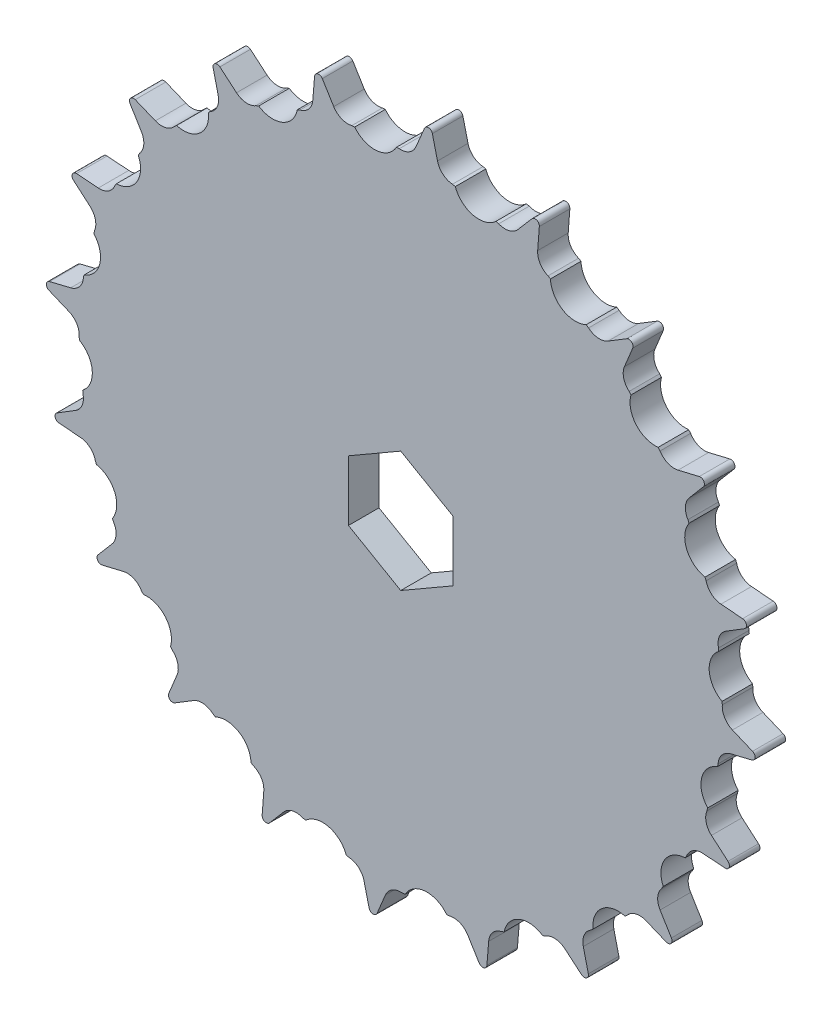
SolidWorks part; units mm, degrees
ref_plane "Front Plane" through (0, 0, 0) normal (0, 0, 1) x (1, 0, 0)
ref_plane "Top Plane" through (0, 0, 0) normal (0, 1, 0) x (1, 0, 0)
ref_plane "Right Plane" through (0, 0, 0) normal (1, 0, 0) x (0, 0, -1)
sketch "Sketch1" plane through (0, 0, 0) normal (0, 0, 1) x (1, 0, 0)
  line L0 (3.6626, 79.3215) -> (5.6677, 84.1262)
  line L1 (3.6626, 79.3215) -> (8.7911, 78.9179) construction
  line L2 (7.5623, 83.9771) -> (8.7911, 78.9179)
  line L3 (3.6626, 79.3215) -> (0, 0) construction
  line L4 (0, 0) -> (8.7911, 78.9179) construction
  line L5 (16.0261, 77.772) -> (18.7582, 82.2038)
  line L6 (20.6061, 81.7602) -> (21.0283, 76.5711)
  line L7 (27.995, 74.3074) -> (31.3867, 78.2573)
  line L8 (33.1425, 77.5301) -> (32.7478, 72.3388)
  line L9 (39.2746, 69.0132) -> (43.2424, 72.3839)
  line L10 (44.8629, 71.3909) -> (43.6609, 66.3253)
  line L11 (49.5871, 62.0196) -> (54.0334, 64.7281)
  line L12 (55.4785, 63.4939) -> (53.4989, 58.6786)
  line L13 (58.6786, 53.4989) -> (63.4939, 55.4785)
  line L14 (64.7281, 54.0334) -> (62.0196, 49.5871)
  line L15 (66.3253, 43.6609) -> (71.3909, 44.8629)
  line L16 (72.3839, 43.2424) -> (69.0132, 39.2746)
  line L17 (72.3388, 32.7478) -> (77.5301, 33.1425)
  line L18 (78.2573, 31.3867) -> (74.3074, 27.995)
  line L19 (76.5711, 21.0283) -> (81.7602, 20.6061)
  line L20 (82.2038, 18.7582) -> (77.772, 16.0261)
  line L21 (78.9179, 8.7911) -> (83.9771, 7.5623)
  line L22 (84.1262, 5.6677) -> (79.3215, 3.6626)
  line L23 (79.3215, -3.6626) -> (84.1262, -5.6677)
  line L24 (83.9771, -7.5623) -> (78.9179, -8.7911)
  line L25 (77.772, -16.0261) -> (82.2038, -18.7582)
  line L26 (81.7602, -20.6061) -> (76.5711, -21.0283)
  line L27 (74.3074, -27.995) -> (78.2573, -31.3867)
  line L28 (77.5301, -33.1425) -> (72.3388, -32.7478)
  line L29 (69.0132, -39.2746) -> (72.3839, -43.2424)
  line L30 (71.3909, -44.8629) -> (66.3253, -43.6609)
  line L31 (62.0196, -49.5871) -> (64.7281, -54.0334)
  line L32 (63.4939, -55.4785) -> (58.6786, -53.4989)
  line L33 (53.4989, -58.6786) -> (55.4785, -63.4939)
  line L34 (54.0334, -64.7281) -> (49.5871, -62.0196)
  line L35 (43.6609, -66.3253) -> (44.8629, -71.3909)
  line L36 (43.2424, -72.3839) -> (39.2746, -69.0132)
  line L37 (32.7478, -72.3388) -> (33.1425, -77.5301)
  line L38 (31.3867, -78.2573) -> (27.995, -74.3074)
  line L39 (21.0283, -76.5711) -> (20.6061, -81.7602)
  line L40 (18.7582, -82.2038) -> (16.0261, -77.772)
  line L41 (8.7911, -78.9179) -> (7.5623, -83.9771)
  line L42 (5.6677, -84.1262) -> (3.6626, -79.3215)
  line L43 (-3.6626, -79.3215) -> (-5.6677, -84.1262)
  line L44 (-7.5623, -83.9771) -> (-8.7911, -78.9179)
  line L45 (-16.0261, -77.772) -> (-18.7582, -82.2038)
  line L46 (-20.6061, -81.7602) -> (-21.0283, -76.5711)
  line L47 (-27.995, -74.3074) -> (-31.3867, -78.2573)
  line L48 (-33.1425, -77.5301) -> (-32.7478, -72.3388)
  line L49 (-39.2746, -69.0132) -> (-43.2424, -72.3839)
  line L50 (-44.8629, -71.3909) -> (-43.6609, -66.3253)
  line L51 (-49.5871, -62.0196) -> (-54.0334, -64.7281)
  line L52 (-55.4785, -63.4939) -> (-53.4989, -58.6786)
  line L53 (-58.6786, -53.4989) -> (-63.4939, -55.4785)
  line L54 (-64.7281, -54.0334) -> (-62.0196, -49.5871)
  line L55 (-66.3253, -43.6609) -> (-71.3909, -44.8629)
  line L56 (-72.3839, -43.2424) -> (-69.0132, -39.2746)
  line L57 (-72.3388, -32.7478) -> (-77.5301, -33.1425)
  line L58 (-78.2573, -31.3867) -> (-74.3074, -27.995)
  line L59 (-76.5711, -21.0283) -> (-81.7602, -20.6061)
  line L60 (-82.2038, -18.7582) -> (-77.772, -16.0261)
  line L61 (-78.9179, -8.7911) -> (-83.9771, -7.5623)
  line L62 (-84.1262, -5.6677) -> (-79.3215, -3.6626)
  line L63 (-79.3215, 3.6626) -> (-84.1262, 5.6677)
  line L64 (-83.9771, 7.5623) -> (-78.9179, 8.7911)
  line L65 (-77.772, 16.0261) -> (-82.2038, 18.7582)
  line L66 (-81.7602, 20.6061) -> (-76.5711, 21.0283)
  line L67 (-74.3074, 27.995) -> (-78.2573, 31.3867)
  line L68 (-77.5301, 33.1425) -> (-72.3388, 32.7478)
  line L69 (-69.0132, 39.2746) -> (-72.3839, 43.2424)
  line L70 (-71.3909, 44.8629) -> (-66.3253, 43.6609)
  line L71 (-62.0196, 49.5871) -> (-64.7281, 54.0334)
  line L72 (-63.4939, 55.4785) -> (-58.6786, 53.4989)
  line L73 (-53.4989, 58.6786) -> (-55.4785, 63.4939)
  line L74 (-54.0334, 64.7281) -> (-49.5871, 62.0196)
  line L75 (-43.6609, 66.3253) -> (-44.8629, 71.3909)
  line L76 (-43.2424, 72.3839) -> (-39.2746, 69.0132)
  line L77 (-32.7478, 72.3388) -> (-33.1425, 77.5301)
  line L78 (-31.3867, 78.2573) -> (-27.995, 74.3074)
  line L79 (-21.0283, 76.5711) -> (-20.6061, 81.7602)
  line L80 (-18.7582, 82.2038) -> (-16.0261, 77.772)
  line L81 (-8.7911, 78.9179) -> (-7.5623, 83.9771)
  line L82 (-5.6677, 84.1262) -> (-3.6626, 79.3215)
  line L83 (0, 80.85) -> (0, 0) construction
  line L84 (0, 0) -> (6.5906, 83.7411) construction
  circle A0 centre (0, 0) radius 80.85 construction
  arc A1 (-3.9676, 80.7526) -> (3.6626, 79.3215) centre (0, 80.85) ccw
  arc A2 (4.2537, 80.738) -> (8.4288, 80.4094) centre (0, 0) cw
  arc A3 (5.6677, 84.1262) -> (7.5623, 83.9771) centre (6.5906, 83.7411) cw
  arc A4 (8.7138, 80.3791) -> (16.0261, 77.772) centre (12.6477, 79.8546) ccw
  arc A5 (18.7582, 82.2038) -> (20.6061, 81.7602) centre (19.6094, 81.6791) cw
  arc A6 (21.1806, 78.0263) -> (27.995, 74.3074) centre (24.984, 76.8929) ccw
  arc A7 (31.3867, 78.2573) -> (33.1425, 77.5301) centre (32.1454, 77.6059) cw
  arc A8 (33.1258, 73.7523) -> (39.2746, 69.0132) centre (36.7051, 72.0379) ccw
  arc A9 (43.2424, 72.3839) -> (44.8629, 71.3909) centre (43.8899, 71.6218) cw
  arc A10 (44.2554, 67.6623) -> (49.5871, 62.0196) centre (47.5224, 65.409) ccw
  arc A11 (54.0334, 64.7281) -> (55.4785, 63.4939) centre (54.5536, 63.8741) cw
  arc A12 (54.2952, 59.9062) -> (58.6786, 53.4989) centre (57.1696, 57.1696) ccw
  arc A13 (63.4939, 55.4785) -> (64.7281, 54.0334) centre (63.8741, 54.5536) cw
  arc A14 (62.9981, 50.675) -> (66.3253, 43.6609) centre (65.409, 47.5224) ccw
  arc A15 (71.3909, 44.8629) -> (72.3839, 43.2424) centre (71.6218, 43.8899) cw
  arc A16 (70.1499, 40.196) -> (72.3388, 32.7478) centre (72.0379, 36.7051) ccw
  arc A17 (77.5301, 33.1425) -> (78.2573, 31.3867) centre (77.6059, 32.1454) cw
  arc A18 (75.5742, 28.7273) -> (76.5711, 21.0283) centre (76.8929, 24.984) ccw
  arc A19 (81.7602, 20.6061) -> (82.2038, 18.7582) centre (81.6791, 19.6094) cw
  arc A20 (79.1377, 16.5512) -> (78.9179, 8.7911) centre (79.8546, 12.6477) ccw
  arc A21 (83.9771, 7.5623) -> (84.1262, 5.6677) centre (83.7411, 6.5906) cw
  arc A22 (80.7526, 3.9676) -> (79.3215, -3.6626) centre (80.85, 0) ccw
  arc A23 (84.1262, -5.6677) -> (83.9771, -7.5623) centre (83.7411, -6.5906) cw
  arc A24 (80.3791, -8.7138) -> (77.772, -16.0261) centre (79.8546, -12.6477) ccw
  arc A25 (82.2038, -18.7582) -> (81.7602, -20.6061) centre (81.6791, -19.6094) cw
  arc A26 (78.0263, -21.1806) -> (74.3074, -27.995) centre (76.8929, -24.984) ccw
  arc A27 (78.2573, -31.3867) -> (77.5301, -33.1425) centre (77.6059, -32.1454) cw
  arc A28 (73.7523, -33.1258) -> (69.0132, -39.2746) centre (72.0379, -36.7051) ccw
  arc A29 (72.3839, -43.2424) -> (71.3909, -44.8629) centre (71.6218, -43.8899) cw
  arc A30 (67.6623, -44.2554) -> (62.0196, -49.5871) centre (65.409, -47.5224) ccw
  arc A31 (64.7281, -54.0334) -> (63.4939, -55.4785) centre (63.8741, -54.5536) cw
  arc A32 (59.9062, -54.2952) -> (53.4989, -58.6786) centre (57.1696, -57.1696) ccw
  arc A33 (55.4785, -63.4939) -> (54.0334, -64.7281) centre (54.5536, -63.8741) cw
  arc A34 (50.675, -62.9981) -> (43.6609, -66.3253) centre (47.5224, -65.409) ccw
  arc A35 (44.8629, -71.3909) -> (43.2424, -72.3839) centre (43.8899, -71.6218) cw
  arc A36 (40.196, -70.1499) -> (32.7478, -72.3388) centre (36.7051, -72.0379) ccw
  arc A37 (33.1425, -77.5301) -> (31.3867, -78.2573) centre (32.1454, -77.6059) cw
  arc A38 (28.7273, -75.5742) -> (21.0283, -76.5711) centre (24.984, -76.8929) ccw
  arc A39 (20.6061, -81.7602) -> (18.7582, -82.2038) centre (19.6094, -81.6791) cw
  arc A40 (16.5512, -79.1377) -> (8.7911, -78.9179) centre (12.6477, -79.8546) ccw
  arc A41 (7.5623, -83.9771) -> (5.6677, -84.1262) centre (6.5906, -83.7411) cw
  arc A42 (3.9676, -80.7526) -> (-3.6626, -79.3215) centre (0, -80.85) ccw
  arc A43 (-5.6677, -84.1262) -> (-7.5623, -83.9771) centre (-6.5906, -83.7411) cw
  arc A44 (-8.7138, -80.3791) -> (-16.0261, -77.772) centre (-12.6477, -79.8546) ccw
  arc A45 (-18.7582, -82.2038) -> (-20.6061, -81.7602) centre (-19.6094, -81.6791) cw
  arc A46 (-21.1806, -78.0263) -> (-27.995, -74.3074) centre (-24.984, -76.8929) ccw
  arc A47 (-31.3867, -78.2573) -> (-33.1425, -77.5301) centre (-32.1454, -77.6059) cw
  arc A48 (-33.1258, -73.7523) -> (-39.2746, -69.0132) centre (-36.7051, -72.0379) ccw
  arc A49 (-43.2424, -72.3839) -> (-44.8629, -71.3909) centre (-43.8899, -71.6218) cw
  arc A50 (-44.2554, -67.6623) -> (-49.5871, -62.0196) centre (-47.5224, -65.409) ccw
  arc A51 (-54.0334, -64.7281) -> (-55.4785, -63.4939) centre (-54.5536, -63.8741) cw
  arc A52 (-54.2952, -59.9062) -> (-58.6786, -53.4989) centre (-57.1696, -57.1696) ccw
  arc A53 (-63.4939, -55.4785) -> (-64.7281, -54.0334) centre (-63.8741, -54.5536) cw
  arc A54 (-62.9981, -50.675) -> (-66.3253, -43.6609) centre (-65.409, -47.5224) ccw
  arc A55 (-71.3909, -44.8629) -> (-72.3839, -43.2424) centre (-71.6218, -43.8899) cw
  arc A56 (-70.1499, -40.196) -> (-72.3388, -32.7478) centre (-72.0379, -36.7051) ccw
  arc A57 (-77.5301, -33.1425) -> (-78.2573, -31.3867) centre (-77.6059, -32.1454) cw
  arc A58 (-75.5742, -28.7273) -> (-76.5711, -21.0283) centre (-76.8929, -24.984) ccw
  arc A59 (-81.7602, -20.6061) -> (-82.2038, -18.7582) centre (-81.6791, -19.6094) cw
  arc A60 (-79.1377, -16.5512) -> (-78.9179, -8.7911) centre (-79.8546, -12.6477) ccw
  arc A61 (-83.9771, -7.5623) -> (-84.1262, -5.6677) centre (-83.7411, -6.5906) cw
  arc A62 (-80.7526, -3.9676) -> (-79.3215, 3.6626) centre (-80.85, 0) ccw
  arc A63 (-84.1262, 5.6677) -> (-83.9771, 7.5623) centre (-83.7411, 6.5906) cw
  arc A64 (-80.3791, 8.7138) -> (-77.772, 16.0261) centre (-79.8546, 12.6477) ccw
  arc A65 (-82.2038, 18.7582) -> (-81.7602, 20.6061) centre (-81.6791, 19.6094) cw
  arc A66 (-78.0263, 21.1806) -> (-74.3074, 27.995) centre (-76.8929, 24.984) ccw
  arc A67 (-78.2573, 31.3867) -> (-77.5301, 33.1425) centre (-77.6059, 32.1454) cw
  arc A68 (-73.7523, 33.1258) -> (-69.0132, 39.2746) centre (-72.0379, 36.7051) ccw
  arc A69 (-72.3839, 43.2424) -> (-71.3909, 44.8629) centre (-71.6218, 43.8899) cw
  arc A70 (-67.6623, 44.2554) -> (-62.0196, 49.5871) centre (-65.409, 47.5224) ccw
  arc A71 (-64.7281, 54.0334) -> (-63.4939, 55.4785) centre (-63.8741, 54.5536) cw
  arc A72 (-59.9062, 54.2952) -> (-53.4989, 58.6786) centre (-57.1696, 57.1696) ccw
  arc A73 (-55.4785, 63.4939) -> (-54.0334, 64.7281) centre (-54.5536, 63.8741) cw
  arc A74 (-50.675, 62.9981) -> (-43.6609, 66.3253) centre (-47.5224, 65.409) ccw
  arc A75 (-44.8629, 71.3909) -> (-43.2424, 72.3839) centre (-43.8899, 71.6218) cw
  arc A76 (-40.196, 70.1499) -> (-32.7478, 72.3388) centre (-36.7051, 72.0379) ccw
  arc A77 (-33.1425, 77.5301) -> (-31.3867, 78.2573) centre (-32.1454, 77.6059) cw
  arc A78 (-28.7273, 75.5742) -> (-21.0283, 76.5711) centre (-24.984, 76.8929) ccw
  arc A79 (-20.6061, 81.7602) -> (-18.7582, 82.2038) centre (-19.6094, 81.6791) cw
  arc A80 (-16.5512, 79.1377) -> (-8.7911, 78.9179) centre (-12.6477, 79.8546) ccw
  arc A81 (-7.5623, 83.9771) -> (-5.6677, 84.1262) centre (-6.5906, 83.7411) cw
  point P289 (0, 0)
  dimension "D1" = 161.7
  dimension "D2" = 3.9688
  dimension "D5" = 1
  dimension "D6" = 84
  dimension "D3" = 4.5
  dimension "D4" = 40
extrude "Boss-Extrude1" add sketch "Sketch1" along normal blind 7.3 contours A81 L81 A80 L80 A79 L79 A78 L78 A77 L77 A76 L76 A75 L75 A74 L74 A73 L73 A72 L72 A71 L71 A70 L70 A69 L69 A68 L68 A67 L67 A66 L66 A65 L65 A64 L64 A63 L63 A62 L62 A61 L61 A60 L60 A59 L59 A58 L58 A57 L57 A56 | A3 L0 A2 L2 region at (-0.0037, -0.0473, 0) region at (6.4765, 82.2915, 0)
sketch "Sketch2" plane through (0, 0, 7.3) normal (0, 0, 1) x (1, 0, 0)
  circle A0 centre (0, 0) radius 12.5
  dimension "D1" = 25
extrude "Boss-Extrude2" add sketch "Sketch2" along normal blind 40
fillet "Fillet1" radius 30 1 edges at (12.5, 0, 7.3)
sketch "Sketch3" plane through (0, 0, 47.3) normal (0, 0, 1) x (1, 0, 0)
  circle A0 centre (0, 0) radius 5
  dimension "D1" = 10
extrude "Cut-Extrude1" cut sketch "Sketch3" against normal through all
hole_wizard "Ø1.0mm Dowel Hole1" positions "3DSketch1" profile "Sketch4" hole size "Ø1.0" standard "ANSI Metric"
sketch3d "3DSketch1"
  point P0 (-6.8176, -10.4771, 42.0201)
  point P2 (-11.0684, 5.8086, 41.6583)
sketch "Sketch4" plane through (-6.8176, -10.4771, 42.0201) normal (0, 0, 1) x (0.8382, -0.5454, 0)
  line L0 (0, 0) -> (0, 34)
  line L1 (0, 34) -> (1.4, 33.1588)
  line L2 (1.4, 33.1588) -> (1.4, 0)
  line L5 (1.4, 0) -> (0, 0)
  line L10 (0, 34) -> (-1.4, 33.1588) construction
  line L11 (0, -6.35) -> (0, 107.95) construction
  dimension "Hole Dia." = 2.8
  dimension "Hole Depth" = 34
  dimension "Drill Angle" = 118
sketch "Sketch5" plane through (0, 0, 0) normal (0, 0, -1) x (-1, 0, 0)
  line L0 (-0.9617, 76.9995) -> (1.0322, 76.8426)
  line L1 (-0.9617, 76.9995) -> (-0.3094, 85.2872)
  line L2 (12.9952, 75.9011) -> (13.6474, 84.1888)
  line L3 (-0.3094, 85.2872) -> (13.6474, 84.1888)
  line L4 (11.0014, 76.058) -> (12.9952, 75.9011)
  arc A0 (1.0322, 76.8426) -> (11.0014, 76.058) centre (6.277, 79.7567) ccw
  arc A2 (7.5623, 83.9771) -> (5.6677, 84.1262) centre (6.5906, 83.7411) ccw construction
  arc A3 (-3.6626, 79.3215) -> (3.6626, 79.3215) centre (0, 80.85) ccw construction
  arc A4 (8.7911, 78.9179) -> (16.0261, 77.772) centre (12.6477, 79.8546) ccw construction
  point P17 (6.669, 84.738)
  dimension "D2" = 2
  dimension "D3" = 2
  dimension "D4" = 6
  dimension "D1" = 14
extrude "Cut-Extrude2" cut sketch "Sketch5" against normal blind 10
pattern_circular "CirPattern1" count 20 over 360 about axis through (0, 0, 0) along (0, 0, 1) of "Cut-Extrude2"
sketch "Sketch7" plane through (0, 0, 0) normal (0, 0, -1) x (-1, 0, 0)
  line L1 (12.5, -7.2169) -> (12.5, 7.2169)
  line L2 (12.5, 7.2169) -> (0, 14.4338)
  line L3 (0, 14.4338) -> (-12.5, 7.2169)
  line L4 (-12.5, 7.2169) -> (-12.5, -7.2169)
  line L5 (-12.5, -7.2169) -> (0, -14.4338)
  line L6 (0, -14.4338) -> (12.5, -7.2169)
  circle A0 centre (0, 0) radius 12.5 construction
  point P1 (0, 0)
  dimension "D1" = 25
extrude "Cut-Extrude3" cut sketch "Sketch7" against normal through all
sketch "Sketch8" plane through (0, 0, 0) normal (0, 1, 0) x (1, 0, 0)
  line L1 (-83.9771, -7.3) -> (90.5942, -7.3)
  line L2 (-83.9771, -7.3) -> (-83.9771, -42.7162)
  line L3 (-83.9771, -42.7162) -> (90.5942, -42.7162)
  line L4 (90.5942, -7.3) -> (90.5942, -42.7162)
extrude "Cut-Extrude4" cut sketch "Sketch8" against normal through all both and the other way through all
